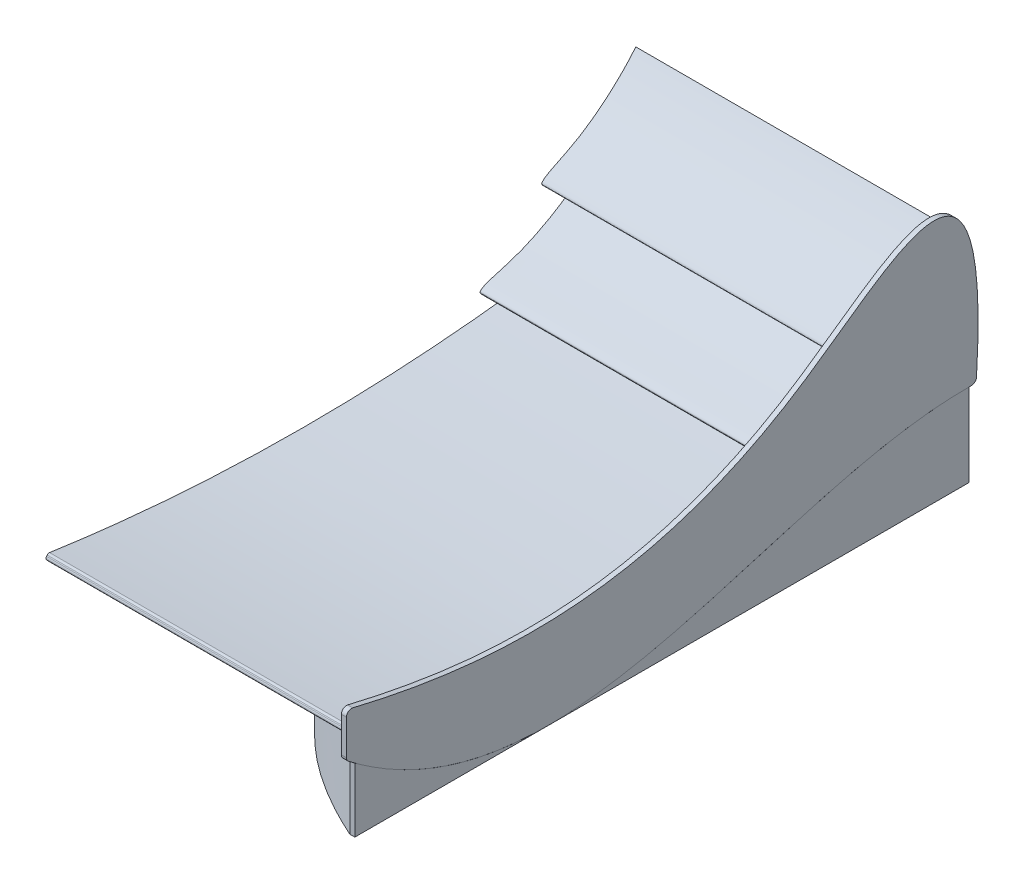
SolidWorks part; units mm, degrees
ref_plane "Front Plane" through (0, 0, 0) normal (0, 0, 1) x (1, 0, 0)
ref_plane "Top Plane" through (0, 0, 0) normal (0, 1, 0) x (1, 0, 0)
ref_plane "Right Plane" through (0, 0, 0) normal (1, 0, 0) x (0, 0, -1)
sketch "Sketch1" plane through (0, 0, 0) normal (1, 0, 0) x (0, 0, -1)
  line L0 (-4.7056, -5.9935) -> (0, 0)
  line L1 (916.65, 23.1498) -> (916.6285, 15.5298)
  line L2 (0, 0) -> (1016, 0) construction
  spline S0 degree 3 poles (0, 0) (306.1844, -240.3919) (601.1445, 24.0377) (916.65, 23.1498) knots 0 0 0 0 1 1 1 1
  spline S1 degree 1 poles (-4.7056, -5.9935) (916.6285, 15.5298) knots 0 0 1 1 construction
  spline S2 degree 3 poles (-4.7056, -5.9935) (-2.2973, -7.8843) (2.5707, -11.6449) (12.2502, -18.8792) (24.3645, -27.4838) (38.888, -37.0952) (53.4082, -46.0172) (67.9227, -54.2642) (87.2683, -64.3833) (111.4364, -75.4295) (140.4124, -86.2561) (169.3576, -94.7913) (198.2666, -101.1752) (236.7571, -107.0087) (284.7575, -109.6403) (342.1739, -106.5159) (399.4367, -98.2863) (456.5967, -86.1175) (513.7126, -71.1626) (589.8852, -49.0301) (685.2737, -20.0903) (781.1854, 3.0497) (848.7408, 12.3244) (887.4742, 15.1008) (906.914, 15.5572) (916.6285, 15.5298) knots 0 0 0 0 0.007812 0.015625 0.03125 0.046875 0.0625 0.078125 0.09375 0.125 0.15625 0.1875 0.21875 0.25 0.3125 0.375 0.4375 0.5 0.5625 0.625 0.75 0.875 0.9375 0.96875 1 1 1 1
  dimension "D2" = 96.52
  dimension "D3" = 355.6
  dimension "D1" = 7.62
extrude "side tray" add sketch "Sketch1" along normal blind 457.2
sketch "Sketch3" plane through (0, 0, 0) normal (1, 0, 0) x (0, 0, -1)
  line L2 (0, 0) -> (1194.0987, 0) construction
  spline S0 degree 3 poles (804.4799, 95.7511) (805.7686, 97.0884) (804.6535, 95.708) (803.9484, 94.5342) (802.3, 91.9646) (800.3836, 89.015) (797.7275, 85.5443) (794.4007, 81.7146) (790.4514, 77.4091) (785.9391, 72.6771) (780.939, 67.5743) (775.5203, 62.1839) (769.7573, 56.5905) (763.7233, 50.8848) (757.482, 45.1674) (751.0934, 39.5398) (744.6183, 34.0953) (738.1029, 28.9357) (731.5935, 24.1534) (725.1055, 19.8348) (718.5907, 16.0985) (712.0501, 12.9566) (705.5118, 10.3607) (699.0191, 8.285) (692.6427, 6.6801) (686.4525, 5.5291) (680.5229, 4.8141) (674.9198, 4.5234) (669.7053, 4.6377) (664.9361, 5.1305) (660.6634, 5.968) (656.9355, 7.1179) (653.7912, 8.5228) (651.2693, 10.1331) (649.4079, 11.8735) (648.4734, 13.305) (648.1143, 14.2562) (648.0069, 14.6707) (647.9527, 15.0587) (647.9387, 15.3252) (647.9559, 15.5295) (647.9725, 15.6761) (648.008, 15.8184) (648.066, 15.9556) (648.1387, 16.0938) (648.2563, 16.2879) (648.4439, 16.5317) (648.7561, 16.8885) (649.5208, 17.6136) (651.2178, 18.8572) (654.1951, 20.462) (658.3493, 22.2369) (663.5611, 24.0796) (669.8445, 26.0227) (677.225, 28.0947) (685.6618, 30.4351) (695.0206, 33.2557) (705.0745, 36.6693) (715.4968, 40.7613) (725.9841, 45.4448) (736.3389, 50.5012) (746.3895, 55.7994) (755.9462, 61.2658) (764.8651, 66.7461) (773.0453, 72.0739) (780.4132, 77.1101) (786.9025, 81.7654) (792.4467, 85.9127) (797.064, 89.5299) (800.5657, 92.3522) (803.3186, 94.7759) (804.4799, 95.7511) (805.7686, 97.0884) (804.6535, 95.708) knots -0.016405 -0.007373 -0.001859 0 0.001827 0.006972 0.01469 0.024341 0.035805 0.049336 0.064967 0.082477 0.101609 0.122072 0.143573 0.165804 0.188453 0.21123 0.233855 0.256071 0.277653 0.298406 0.31834 0.337635 0.356359 0.374528 0.392084 0.408886 0.424825 0.439792 0.453698 0.466477 0.478073 0.488448 0.497596 0.505523 0.512253 0.517843 0.518966 0.520373 0.521254 0.522096 0.522498 0.522892 0.523275 0.523665 0.52408 0.524522 0.525478 0.526533 0.52831 0.533889 0.543287 0.555281 0.569972 0.587455 0.607847 0.631247 0.657443 0.685971 0.716097 0.746911 0.777758 0.808197 0.837716 0.865748 0.891864 0.915741 0.937097 0.955656 0.971217 0.983595 0.992627 0.998141 1 1.001827 1.006972 1.01469 only from (805.5234, 96.8103) to (805.5234, 96.8103)
  spline S1 degree 3 poles (880.5328, 215.7747) (881.5697, 217.3155) (880.7112, 215.7624) (880.2207, 214.484) (879.0435, 211.6672) (877.6684, 208.4296) (875.6553, 204.5505) (873.0441, 200.2012) (869.9024, 195.2754) (866.2804, 189.8317) (862.2423, 183.9382) (857.842, 177.6887) (853.1379, 171.1796) (848.1863, 164.5127) (843.0326, 157.7984) (837.7183, 151.147) (832.287, 144.6607) (826.7665, 138.4482) (821.1865, 132.6082) (815.5469, 127.2286) (809.7799, 122.4177) (803.8843, 118.1878) (797.8961, 114.4959) (791.8625, 111.3244) (785.8617, 108.6366) (779.9654, 106.4282) (774.25, 104.6944) (768.7825, 103.4351) (763.6274, 102.6422) (758.8451, 102.2994) (754.4918, 102.3822) (750.6209, 102.8673) (747.2804, 103.7048) (744.5172, 104.8527) (742.3818, 106.2435) (741.213, 107.4909) (740.6941, 108.3653) (740.5164, 108.7549) (740.3956, 109.1276) (740.3356, 109.3876) (740.3171, 109.5917) (740.308, 109.7391) (740.3182, 109.8853) (740.3515, 110.0305) (740.3991, 110.1792) (740.4812, 110.3908) (740.6236, 110.6634) (740.8691, 111.0691) (741.4963, 111.916) (742.9516, 113.4354) (745.6049, 115.5328) (749.3878, 118.0021) (754.2005, 120.7218) (760.051, 123.7265) (766.9595, 127.0486) (774.8618, 130.8185) (783.5886, 135.2213) (792.897, 140.3289) (802.4504, 146.1686) (811.9651, 152.602) (821.2845, 159.3797) (830.2624, 166.3427) (838.7247, 173.3855) (846.5564, 180.3313) (853.6872, 186.9987) (860.0687, 193.2378) (865.651, 198.9492) (870.3908, 203.9963) (874.3098, 208.3603) (877.2682, 211.7478) (879.5585, 214.6127) (880.5328, 215.7747) (881.5697, 217.3155) (880.7112, 215.7624) knots -0.016405 -0.007373 -0.001859 0 0.001827 0.006972 0.01469 0.024341 0.035805 0.049336 0.064967 0.082477 0.101609 0.122072 0.143573 0.165804 0.188453 0.21123 0.233855 0.256071 0.277653 0.298406 0.31834 0.337635 0.356359 0.374528 0.392084 0.408886 0.424825 0.439792 0.453698 0.466477 0.478073 0.488448 0.497596 0.505523 0.512253 0.517843 0.518966 0.520373 0.521254 0.522096 0.522498 0.522892 0.523275 0.523665 0.52408 0.524522 0.525478 0.526533 0.52831 0.533889 0.543287 0.555281 0.569972 0.587455 0.607847 0.631247 0.657443 0.685971 0.716097 0.746911 0.777758 0.808197 0.837716 0.865748 0.891864 0.915741 0.937097 0.955656 0.971217 0.983595 0.992627 0.998141 1 1.001827 1.006972 1.01469 only from (881.3765, 216.999) to (881.3765, 216.999)
extrude "Side airfoils" add sketch "Sketch3" along normal blind 457.2 separate body
sketch "Sketch4" plane through (457.2, 0, 0) normal (1, 0, 0) x (0, 0, -1)
  line L0 (-17.3667, 37.749) -> (-17.3667, -28.3308)
  spline S0 degree 3 poles (-17.3667, 37.749) (217.7852, -20.167) (594.5757, -28.3157) (952.0802, 372.4812) (927.2117, -10.0088) knots 0 0 0 0 0.596641 1 1 1 1
  spline S3 degree 3 poles (2440.992, -1739.1178) (-255.4973, 220.9028) (-130.2089, 57.3934) (-10.2709, -33.7578) (-7.742, -35.6479) (-0.1507, -41.2275) (4.9193, -44.8288) (20.1404, -55.2712) (30.301, -61.7499) (60.8343, -79.805) (81.2504, -89.9922) (122.1272, -106.9712) (142.5859, -113.7616) (183.4324, -124.2947) (203.8181, -128.0377) (244.415, -132.8835) (264.625, -133.9874) (304.8138, -133.9991) (324.7926, -132.9076) (364.5092, -128.9753) (384.2481, -126.1349) (423.5067, -119.1361) (443.0275, -114.9777) (481.8828, -105.7553) (501.2184, -100.691) (539.7357, -90.0526) (558.9181, -84.4783) (597.1554, -73.2045) (616.2111, -67.5046) (654.2118, -56.3534) (673.1567, -50.902) (710.9442, -40.6147) (729.7879, -35.7785) (767.3791, -27.0741) (786.1263, -23.206) (823.5287, -16.7801) (842.1849, -14.222) (870.107, -11.6112) (879.4035, -10.9453) (1286.3853, 8.3995) (1683.6754, -382.9269) (93.4099, -2727.9132) knots -0.354099 -0.354099 -0.354099 -0.354099 0.007813 0.007813 0.015625 0.015625 0.03125 0.03125 0.0625 0.0625 0.125 0.125 0.1875 0.1875 0.25 0.25 0.3125 0.3125 0.375 0.375 0.4375 0.4375 0.5 0.5 0.5625 0.5625 0.625 0.625 0.6875 0.6875 0.75 0.75 0.8125 0.8125 0.875 0.875 0.9375 0.9375 0.96875 0.96875 2.3058 2.3058 2.3058 2.3058 only from (-20.3909, -25.9717) to (916.557, -9.8701)
  spline S4 degree 3 poles (-17.3667, -28.3308) (-15.849, -29.5071) (-14.3265, -30.6756) (-10.2709, -33.7578) (-7.742, -35.6479) (-0.1507, -41.2275) (4.9193, -44.8288) (20.1404, -55.2712) (30.301, -61.7499) (60.8343, -79.805) (81.2504, -89.9922) (122.1272, -106.9712) (142.5859, -113.7616) (183.4324, -124.2947) (203.8181, -128.0377) (244.415, -132.8835) (264.625, -133.9874) (304.8138, -133.9991) (324.7926, -132.9076) (364.5092, -128.9753) (384.2481, -126.1349) (423.5067, -119.1361) (443.0275, -114.9777) (481.8828, -105.7553) (501.2184, -100.691) (539.7357, -90.0526) (558.9181, -84.4783) (597.1554, -73.2045) (616.2111, -67.5046) (654.2118, -56.3534) (673.1567, -50.902) (710.9442, -40.6147) (729.7879, -35.7785) (767.3791, -27.0741) (786.1263, -23.206) (823.5287, -16.7801) (842.1849, -14.222) (870.107, -11.6112) (879.4035, -10.9453) (901.559, -9.8922) (914.4192, -9.7099) (927.2117, -10.0088) knots 0.003123 0.003123 0.003123 0.003123 0.007813 0.007813 0.015625 0.015625 0.03125 0.03125 0.0625 0.0625 0.125 0.125 0.1875 0.1875 0.25 0.25 0.3125 0.3125 0.375 0.375 0.4375 0.4375 0.5 0.5 0.5625 0.5625 0.625 0.625 0.6875 0.6875 0.75 0.75 0.8125 0.8125 0.875 0.875 0.9375 0.9375 0.96875 0.96875 1.011988 1.011988 1.011988 1.011988
  dimension "D1" = 25.4
extrude "Side Tower" add sketch "Sketch4" along normal blind 7.62
ref_plane "Plane1" through (0, -134.112, 0) normal (0, 1, 0) x (1, 0, 0)
sketch "Sketch5" plane through (0, -134.112, 0) normal (0, 1, 0) x (1, 0, 0)
  line L1 (0, 332.108) -> (674.8347, 332.108) construction
  line L2 (0, 916.6285) -> (0, -4.7056) construction
  line L3 (457.2, 916.6285) -> (0, 916.6285) construction
  line L7 (457.2, 927.2117) -> (457.2, -17.3667) construction
  line L14 (464.7946, -17.3667) -> (464.7946, 927.2117)
  line L15 (464.7946, -4.7056) -> (464.7946, 916.6285)
  line L16 (464.7946, 916.6285) -> (358.0657, 916.6285)
  line L17 (457.2, -4.7056) -> (0, -4.7056) construction
  line L18 (457.2, -4.7056) -> (464.7946, -4.7056)
  spline S0 degree 3 poles (457.2, -4.7056) (7.7481, 196.5342) (266.5101, 622.3779) (358.0657, 916.6285) knots 0 0 0 0 1 1 1 1
  dimension "D1" = 0.0254
extrude "Boss-Extrude1" add sketch "Sketch5" along normal up to body
fillet "Fillet1" radius 7.62 3 edges at (461.01, 37.749, 17.3667)
sketch "Sketch6" plane through (0, 0, 0) normal (1, 0, 0) x (0, 0, -1)
  line L0 (702.5211, -8.7914) -> (703.4465, -16.3551)
  line L1 (0, 0) -> (-1.1009, -7.54)
  spline S0 degree 3 poles (1975.7952, -1610.7373) (885.8263, 2122.0753) (208.3629, -2327.8849) (-749.6015, 1838.7904) knots -1.016463 -1.016463 -1.016463 -1.016463 1.777635 1.777635 1.777635 1.777635 only from (916.65, 23.1498) to (0, 0) construction
  spline S1 degree 3 poles (916.65, 23.1498) (601.1445, 24.0377) (306.1844, -240.3919) (0, 0) knots 0 0 0 0 1 1 1 1 construction
  spline S2 degree 2 poles (0, 0) (353.0375, -51.5476) (702.5211, -8.7914) knots 0 0 0 1 1 1
  spline S3 degree 3 poles (916.65, 23.1498) (601.1445, 24.0377) (306.1844, -240.3919) (0, 0) knots 0 0 0 0 1 1 1 1 construction
  spline S4 degree 1 poles (-1.1009, -7.54) (703.4465, -16.3551) knots 0 0 1 1 construction
  spline S5 degree 2 poles (-1.1009, -7.54) (352.9346, -59.2346) (703.4465, -16.3551) knots 0 0 0 1 1 1
  dimension "D1" = 7.62
extrude "Boss-Extrude2" add sketch "Sketch6" along normal up to surface (457.2 mm away)
fillet "Fillet2" radius 3.81 2 edges at (228.6, -5.9935, 4.7056) (228.6, 0, 0)
